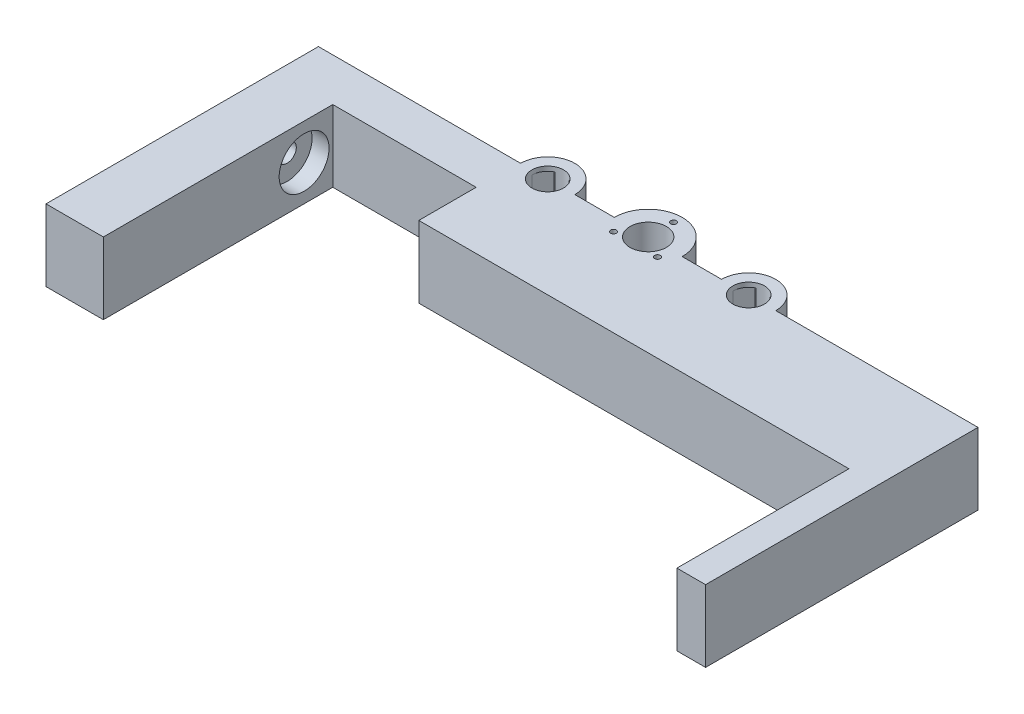
SolidWorks part; units mm, degrees
ref_plane "Front Plane" through (0, 0, 0) normal (0, 0, 1) x (1, 0, 0)
ref_plane "Top Plane" through (0, 0, 0) normal (0, 1, 0) x (1, 0, 0)
ref_plane "Right Plane" through (0, 0, 0) normal (1, 0, 0) x (0, 0, -1)
sketch "Sketch1" plane through (0, 0, 0) normal (0, 1, 0) x (1, 0, 0)
  line L1 (0, 0) -> (0, 11.25)
  line L2 (-146.05, 0) -> (-56.5, 0)
  line L3 (146.05, 0) -> (146.05, -120.65)
  line L4 (-32.5, 0) -> (-15.05, 0) construction
  line L5 (-32.5, 0) -> (-15.05, 0)
  line L6 (15.05, 0) -> (32.5, 0)
  line L7 (15.05, 0) -> (32.5, 0) construction
  line L8 (146.05, -120.65) -> (133.35, -120.65)
  line L9 (133.35, -120.65) -> (133.35, -44.45)
  line L10 (133.35, -44.45) -> (-57.15, -44.45)
  line L11 (-57.15, -44.45) -> (-57.15, -19.05)
  line L12 (-57.15, -19.05) -> (-120.65, -19.05)
  line L13 (-120.65, -19.05) -> (-120.65, -120.65)
  line L14 (-120.65, -120.65) -> (-146.05, -120.65)
  line L15 (-146.05, -120.65) -> (-146.05, 0)
  line L16 (56.5, 0) -> (146.05, 0)
  circle A0 centre (0, 0) radius 8.05
  circle A1 centre (-44.5, 0) radius 7
  circle A2 centre (44.5, 0) radius 7
  circle A3 centre (0, 11.25) radius 1.25
  circle A4 centre (9.7428, -5.625) radius 1.25
  circle A5 centre (-9.7428, -5.625) radius 1.25
  arc A6 (-32.5, 0) -> (-56.5, 0) centre (-44.5, 0) ccw
  arc A7 (56.5, 0) -> (32.5, 0) centre (44.5, 0) ccw
  arc A8 (15.05, 0) -> (-15.05, 0) centre (0, 0) ccw
  circle A9 centre (-44.5, 0) radius 12 construction
  circle A10 centre (0, 0) radius 15.05 construction
  circle A11 centre (44.5, 0) radius 12 construction
  point P4 (0, 0)
  point P17 (0, 0)
  point P26 (0, 0)
  point P31 (0, 0)
  dimension "D2" = 16.1
  dimension "D3" = 2.5
  dimension "D5" = 14
  dimension "D4" = 11.25
  dimension "D6" = 44.5
  dimension "D9" = 254
  dimension "D10" = 63.5
  dimension "D11" = 19.05
  dimension "D12" = 25.4
  dimension "D13" = 76.2
  dimension "D14" = 12.7
  dimension "D15" = 25.4
  dimension "D16" = 0
  dimension "D17" = 44.5
  dimension "D7" = 5
  dimension "D8" = 7
  dimension "D1" = 3
extrude "Boss-Extrude1" add sketch "Sketch1" along normal mid plane 31.75 contours L6 A8 L5 A6 L2 L15 L14 L13 L12 L11 L10 L9 L8 L3 L16 A7 A1 A2 A3 A0 A4 A5 region at (1.4072, 0, 32.4564)
ref_plane "Plane1" through (0, 0, 0) normal (0, 1, 0) x (1, 0, 0)
ref_plane "Plane2" through (0, 0, 31.75) normal (0, 0, 1) x (1, 0, 0)
ref_axis "Axis1" through (-160.655, 0, 31.75) along (1, 0, 0)
sketch "Sketch2" plane through (-146.05, 0, 0) normal (-1, 0, 0) x (0, 0, 1)
  circle A0 centre (31.75, 0) radius 11.05
  dimension "D1" = 22.1
extrude "Cut-Extrude1" cut sketch "Sketch2" against normal blind 7.5
sketch "Sketch3" plane through (-120.65, 0, 0) normal (1, 0, 0) x (0, 0, -1)
  circle A0 centre (-31.75, 0) radius 11.05 construction
  circle A1 centre (-31.75, 0) radius 11.05
extrude "Cut-Extrude3" cut sketch "Sketch3" against normal blind 7.5
sketch "Sketch4" plane through (-138.55, 0, 0) normal (-1, 0, 0) x (0, 0, 1)
  circle A0 centre (31.75, 0) radius 4.05
  dimension "D1" = 8.1
extrude "Cut-Extrude4" cut sketch "Sketch4" against normal up to surface (10.4 mm away) up to face at (-128.15, 0, 20.7)
sketch "Sketch5" plane through (0, 0, 0) normal (0, 0, -1) x (-1, 0, 0)
  line L0 (-51.5, 13.875) -> (-51.5, -13.875)
  line L1 (-44.5, 15.875) -> (-44.5, -15.875) construction
  line L2 (-51.5, 13.875) -> (-47.5, 13.875)
  line L3 (-47.5, 13.875) -> (-47.5, -13.875)
  line L4 (-47.5, -13.875) -> (-51.5, -13.875)
  line L5 (-32.5, 15.875) -> (-56.5, 15.875) construction
  line L7 (-56.5, -15.875) -> (-32.5, -15.875) construction
  line L8 (0, 15.875) -> (0, -16.3974) construction
  line L9 (-41.5, 13.875) -> (-37.5, 13.875)
  line L10 (-41.5, 13.875) -> (-41.5, -13.875)
  line L11 (-41.5, -13.875) -> (-37.5, -13.875)
  line L12 (-37.5, 13.875) -> (-37.5, -13.875)
  line L13 (15.05, 15.875) -> (-15.05, 15.875) construction
  line L14 (0, 15.875) -> (0, -15.875) construction
  line L15 (47.5, -13.875) -> (51.5, -13.875)
  line L16 (51.5, 13.875) -> (51.5, -13.875)
  line L17 (51.5, 13.875) -> (47.5, 13.875)
  line L18 (47.5, 13.875) -> (47.5, -13.875)
  line L19 (41.5, -13.875) -> (37.5, -13.875)
  line L20 (41.5, 13.875) -> (41.5, -13.875)
  line L21 (41.5, 13.875) -> (37.5, 13.875)
  line L22 (37.5, 13.875) -> (37.5, -13.875)
  dimension "D1" = 7
  dimension "D2" = 2
  dimension "D3" = 2
  dimension "D4" = 4
  dimension "D5" = 7
extrude "Cut-Extrude5" cut sketch "Sketch5" along normal through all
